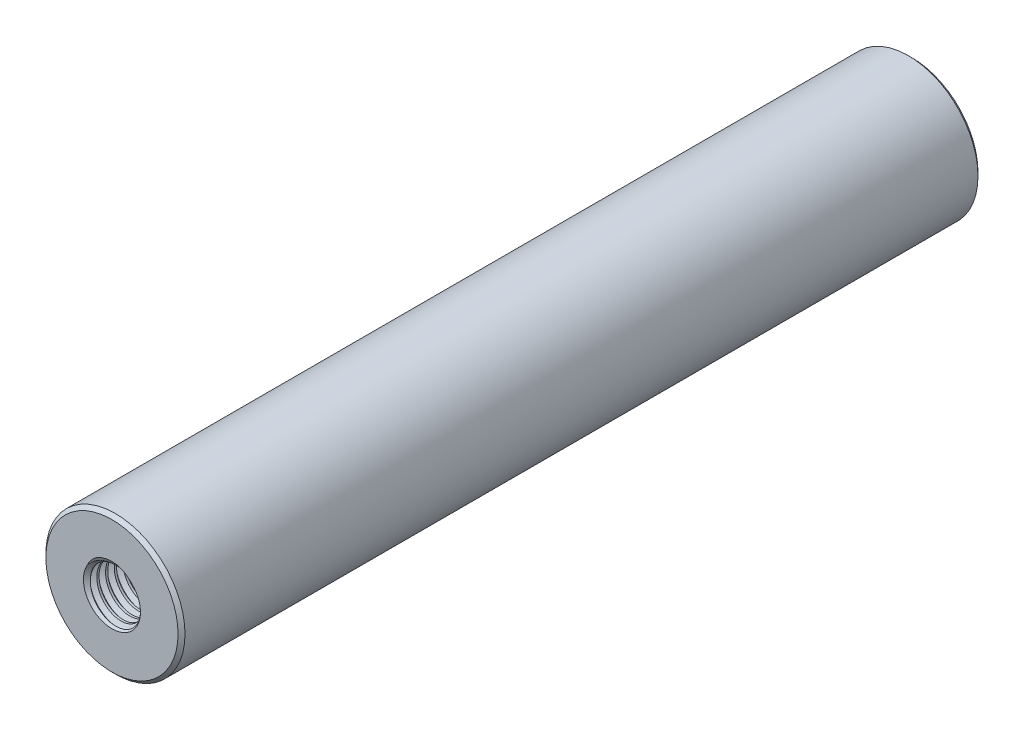
SolidWorks part; units mm, degrees
material "1060 slitina"
ref_plane "Přední rovina" through (0, 0, 0) normal (0, 0, 1) x (1, 0, 0)
ref_plane "Horní rovina" through (0, 0, 0) normal (0, 1, 0) x (1, 0, 0)
ref_plane "Pravá rovina" through (0, 0, 0) normal (1, 0, 0) x (0, 0, -1)
sketch "Skica1" plane through (0, 0, 0) normal (0, 0, 1) x (1, 0, 0)
  circle A0 centre (0, 0) radius 3.6
  circle A1 centre (0, 0) radius 10
  dimension "D1" = 7.2
  dimension "D2" = 20
extrude "Přidat vysunutím1" add sketch "Skica1" along normal blind 115
chamfer "Zkosení1" distance 0.5 angle 45 4 edges at (3.6, 0, 0) (10, 0, 0) (3.6, 0, 115) (10, 0, 115)
thread "Závit1" pitch 1.25 method cut profile "Profil závitu1" start angle 0, offset 5, length 40, pitch 1.25, diameter 7.2
ref_plane "Rovina1" through (-3.6, 0, 119.5) normal (0, -1, 0) x (-1, 0, 0)
sketch "Profil závitu1" plane through (-3.6, 0, 119.5) normal (0, -1, 0) x (-1, 0, 0)
  line L0 (0, 0) -> (0, 1.25) construction
  line L1 (0, 0) -> (0.6766, 0.3906)
  line L2 (0.6766, 0.3906) -> (0.6766, 0.5469)
  line L3 (0.6766, 0.5469) -> (0, 0.9375)
  line L4 (0.6766, 0.4687) -> (0, 0.4687) construction
  line L11 (0, 0) -> (0, 0.9375)
  point P2 (0, 0)
  dimension "Pitch" = 1.25
  dimension "Profile_Angle" = 60
  dimension "Profile_Land" = 0.1562
  dimension "Profile_Height" = 0.6766
thread "Závit2" pitch 1.25 method cut profile "Profil závitu2" start angle 0, offset 5, length 40, pitch 1.25, diameter 7.2
ref_plane "Rovina2" through (3.6, 0, -4.5) normal (0, -1, 0) x (1, 0, 0)
sketch "Profil závitu2" plane through (3.6, 0, -4.5) normal (0, -1, 0) x (1, 0, 0)
  line L0 (0, 0) -> (0, 1.25) construction
  line L1 (0, 0) -> (0.6766, 0.3906)
  line L2 (0.6766, 0.3906) -> (0.6766, 0.5469)
  line L3 (0.6766, 0.5469) -> (0, 0.9375)
  line L4 (0.6766, 0.4687) -> (0, 0.4687) construction
  line L11 (0, 0) -> (0, 0.9375)
  point P2 (0, 0)
  dimension "Pitch" = 1.25
  dimension "Profile_Angle" = 60
  dimension "Profile_Land" = 0.1562
  dimension "Profile_Height" = 0.6766
